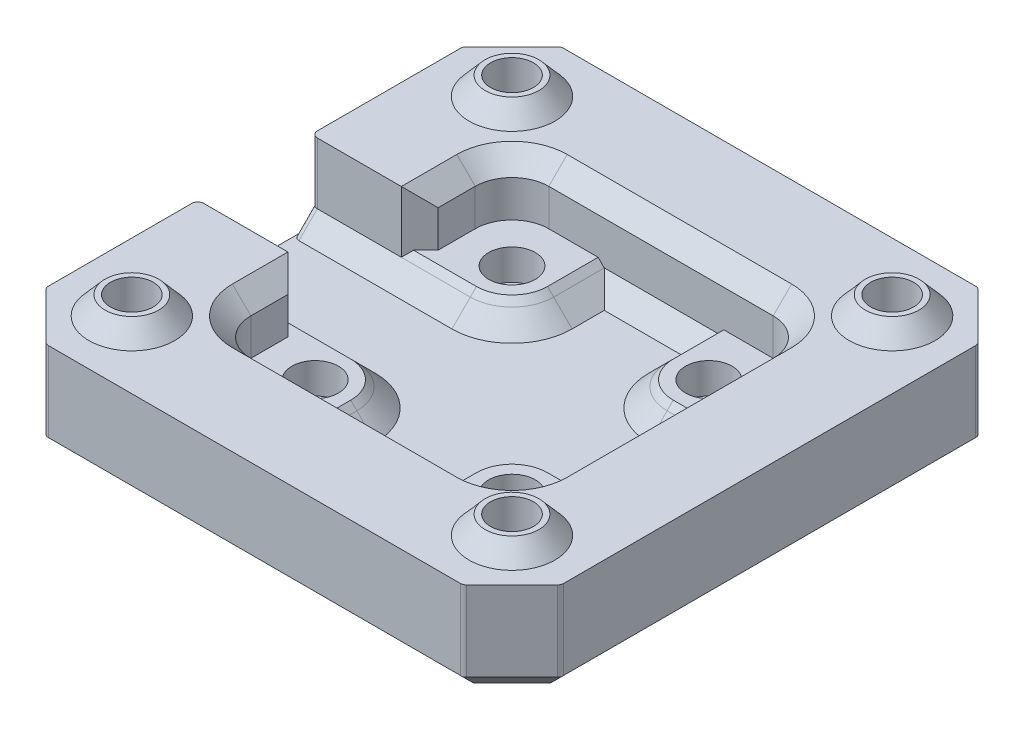
SolidWorks part; units mm, degrees
material "ABS"
ref_plane "Front Plane" through (0, 0, 0) normal (0, 0, 1) x (1, 0, 0)
ref_plane "Top Plane" through (0, 0, 0) normal (0, 1, 0) x (1, 0, 0)
ref_plane "Right Plane" through (0, 0, 0) normal (1, 0, 0) x (0, 0, -1)
sketch "Sketch1" plane through (0, 0, 0) normal (0, 1, 0) x (1, 0, 0)
  line L8 (-17, 21) -> (-21, 17)
  line L9 (17, -21) -> (-17, -21)
  line L10 (21, -17) -> (21, 17)
  line L11 (17, 21) -> (-17, 21)
  line L12 (-21, -17) -> (-21, 17)
  line L13 (21, 17) -> (17, 21)
  line L14 (21, -17) -> (17, -21)
  line L15 (-17, -21) -> (-21, -17)
  point P0 (21, -21)
  point P1 (-21, 21)
  point P2 (21, 21)
  point P3 (-21, -21)
  point P12 (21, 0)
  point P14 (0, 21)
  dimension "D1" = 42
extrude "Base Extrude" add sketch "Sketch1" along normal blind 8
chamfer "Back Chamfer" distance 1.5 angle 45 8 edges at (-19, 0, -19) (-21, 0, 0) (-19, 0, 19) (0, 0, 21) (0, 0, -21) (19, 0, -19) (21, 0, 0) (19, 0, 19)
sketch "Sketch2" plane through (0, 8, 0) normal (0, 1, 0) x (1, 0, 0)
  circle A0 centre (-15.5, 15.5) radius 1.75
  circle A1 centre (15.5, 15.5) radius 1.75
  circle A2 centre (15.5, -15.5) radius 1.75
  circle A3 centre (-15.5, -15.5) radius 1.75
  point P12 (0, 0)
  dimension "D3" = 3.5
  dimension "D1" = 15.5
  dimension "D2" = 15.5
  dimension "D4" = 4
extrude "Motor Screw Hole2" cut sketch "Sketch2" against normal through all
ref_plane "Motor Screw Hole Plane" through (0, 0, 15.5) normal (0, 0, 1) x (1, 0, 0)
sketch "Sketch6" plane through (0, 0, 15.5) normal (0, 0, 1) x (1, 0, 0)
  line L0 (-15.5, -992) -> (-15.5, 49008) construction
  line L1 (-13.75, 8) -> (-17.25, 8) construction
  line L2 (-18.25, 0) -> (-17, 2)
  line L3 (-15.5, 0) -> (-18.25, 0)
  line L4 (-17.25, 0) -> (-13.75, 0) construction
  line L8 (-15.5, 2) -> (-15.5, 0)
  line L10 (-17, 2) -> (-15.5, 2)
  point P5 (-15.5, 8)
  point P7 (-15.5, 2)
  dimension "D1" = 5.5
  dimension "D2" = 2
  dimension "D3" = 3
revolve "Motor Screw Entry Chamfer" cut sketch "Sketch6" angle 360 about L0
sketch "Sketch11" plane through (0, 0, 15.5) normal (0, 0, 1) x (1, 0, 0)
  line L0 (-15.5, -992) -> (-15.5, 49008) construction
  line L1 (-13.75, 8) -> (-17.25, 8) construction
  line L2 (-17.25, 8) -> (-17.25, 9.5)
  line L3 (-17.6875, 9.5) -> (-19, 8)
  line L4 (-17, 8) -> (-21, 8) construction
  line L5 (-19, 8) -> (-17.25, 8)
  line L6 (-17.25, 9.5) -> (-17.6875, 9.5)
  line L7 (-17.25, 9.5) -> (-17.25, 10) construction
  line L8 (-17.25, 10) -> (-17.6875, 9.5) construction
  point P5 (-15.5, 8)
  dimension "D1" = 2
  dimension "D2" = 7
  dimension "D3" = 0.5
revolve "Motor Screw Alignment Revolve" add sketch "Sketch11" angle 360 about L0
mirror "Motor Screw Pattern" about plane through (0, 0, 0) normal (1, 0, 0) of "Motor Screw Alignment Revolve", "Motor Screw Entry Chamfer" second plane through (0, 0, 0) second plane normal (0, 0, 1)
sketch "Sketch3" plane through (0, 8, 0) normal (0, 1, 0) x (1, 0, 0)
  line L1 (-9.15, -12.15) -> (9.15, -12.15)
  line L2 (-12.15, -9.15) -> (-12.15, 9.15)
  line L3 (-9.15, 12.15) -> (9.15, 12.15)
  line L4 (12.15, -9.15) -> (12.15, 9.15)
  line L5 (-12.15, -12.15) -> (12.15, 12.15) construction
  line L6 (-12.15, 12.15) -> (12.15, -12.15) construction
  arc A0 (-9.15, -12.15) -> (-12.15, -9.15) centre (-9.15, -9.15) cw
  arc A1 (9.15, -12.15) -> (12.15, -9.15) centre (9.15, -9.15) ccw
  arc A2 (9.15, 12.15) -> (12.15, 9.15) centre (9.15, 9.15) cw
  arc A3 (-12.15, 9.15) -> (-9.15, 12.15) centre (-9.15, 9.15) cw
  point P0 (0, 0)
  dimension "D2" = 3
  dimension "D1" = 24.3
extrude "Sensor Holder Cut" cut sketch "Sketch3" against normal blind 4.5
sketch "Sketch5" plane through (0, 3.5, 0) normal (0, 1, 0) x (1, 0, 0)
  circle A0 centre (-8.025, 8.025) radius 1.9
  circle A1 centre (8.025, 8.025) radius 1.9
  circle A2 centre (8.025, -8.025) radius 1.9
  circle A3 centre (-8.025, -8.025) radius 1.9
  point P12 (0, 0)
  dimension "D3" = 3.8
  dimension "D1" = 8.025
  dimension "D2" = 8.025
  dimension "D4" = 4
extrude "Sensor Holder Holes" cut sketch "Sketch5" against normal blind 2.5
sketch "Sketch8" plane through (0, 3.5, 0) normal (0, 1, 0) x (1, 0, 0)
  line L0 (-12.15, 4.625) -> (-8.025, 4.625)
  line L1 (-12.15, 9.15) -> (-12.15, -9.15) construction
  line L2 (-4.625, 8.025) -> (-4.625, 12.15)
  line L3 (9.15, 12.15) -> (-9.15, 12.15) construction
  line L4 (8.025, 4.625) -> (12.15, 4.625)
  line L5 (4.625, 12.15) -> (4.625, 8.025)
  line L6 (4.625, -8.025) -> (4.625, -12.15)
  line L7 (12.15, -4.625) -> (8.025, -4.625)
  line L8 (-8.025, -4.625) -> (-12.15, -4.625)
  line L9 (-4.625, -12.15) -> (-4.625, -8.025)
  line L10 (-12.15, 4.625) -> (-12.15, -4.625)
  line L11 (-4.625, -12.15) -> (4.625, -12.15)
  line L12 (12.15, -4.625) -> (12.15, 4.625)
  line L13 (4.625, 12.15) -> (-4.625, 12.15)
  circle A0 centre (-8.025, 8.025) radius 1.9 construction
  circle A1 centre (-8.025, 8.025) radius 1.9 construction
  arc A2 (-8.025, 4.625) -> (-4.625, 8.025) centre (-8.025, 8.025) ccw
  arc A3 (4.625, 8.025) -> (8.025, 4.625) centre (8.025, 8.025) ccw
  arc A4 (8.025, -4.625) -> (4.625, -8.025) centre (8.025, -8.025) ccw
  arc A5 (-4.625, -8.025) -> (-8.025, -4.625) centre (-8.025, -8.025) ccw
  point P30 (0, 0)
  dimension "D1" = 1.5
  dimension "D2" = 4
extrude "Wire Spacer Cut" cut sketch "Sketch8" against normal blind 2
sketch "Sketch9" plane through (0, 1.5, 0) normal (0, 1, 0) x (1, 0, 0)
  line L0 (-12.15, -4.625) -> (-8.025, -4.625) construction
  line L1 (-8.025, 4.625) -> (-21, 4.625)
  line L2 (-8.025, 4.625) -> (-8.025, -4.625)
  line L3 (-8.025, -4.625) -> (-21, -4.625)
  line L4 (-21, 4.625) -> (-21, -4.625)
  line L5 (-21, 17) -> (-21, -17) construction
extrude "Wire Output Cut" cut sketch "Sketch9" along normal through all
chamfer "Large Internal Chamfers" distance 1.5 angle 45 26 edges at (0, 1.5, 12.15) (4.625, 1.5, 10.0875) (10.0875, 1.5, 4.625) (5.6208, 1.5, 5.6208) (12.15, 1.5, 0) (10.0875, 1.5, -4.625) (5.6208, 1.5, -5.6208) (4.625, 1.5, -10.0875) (0, 1.5, -12.15) (-4.625, 1.5, 10.0875) (-5.6208, 1.5, 5.6208) (-14.5125, 1.5, 4.625) (-4.625, 1.5, -10.0875) (-5.6208, 1.5, -5.6208) (-14.5125, 1.5, -4.625) (-12.15, 8, 6.8875) (-11.2713, 8, 11.2713) (0, 8, 12.15) (11.2713, 8, 11.2713) (12.15, 8, 0) (-12.15, 8, -6.8875) (11.2713, 8, -11.2713) (-11.2713, 8, -11.2713) (0, 8, -12.15) (-12.15, 5.75, 4.625) (-12.15, 5.75, -4.625)
chamfer "Small Internal Chamfers" distance 0.5 angle 45 12 edges at (-10.8375, 3.5, 4.625) (-4.625, 3.5, 10.0875) (-5.6208, 3.5, 5.6208) (4.625, 3.5, 10.0875) (10.0875, 3.5, 4.625) (5.6208, 3.5, 5.6208) (10.0875, 3.5, -4.625) (4.625, 3.5, -10.0875) (5.6208, 3.5, -5.6208) (-4.625, 3.5, -10.0875) (-10.8375, 3.5, -4.625) (-5.6208, 3.5, -5.6208)
fillet "Exterier Edge Fillets" radius 0.5 12 edges at (-21, 5.5, -4.625) (-21, 2.25, -3.875) (-21, 2.25, 3.875) (-21, 5.5, 4.625) (21, 4.75, -17) (17, 4.75, -21) (-17, 4.75, -21) (-21, 4.75, -17) (-21, 4.75, 17) (-17, 4.75, 21) (17, 4.75, 21) (21, 4.75, 17)
